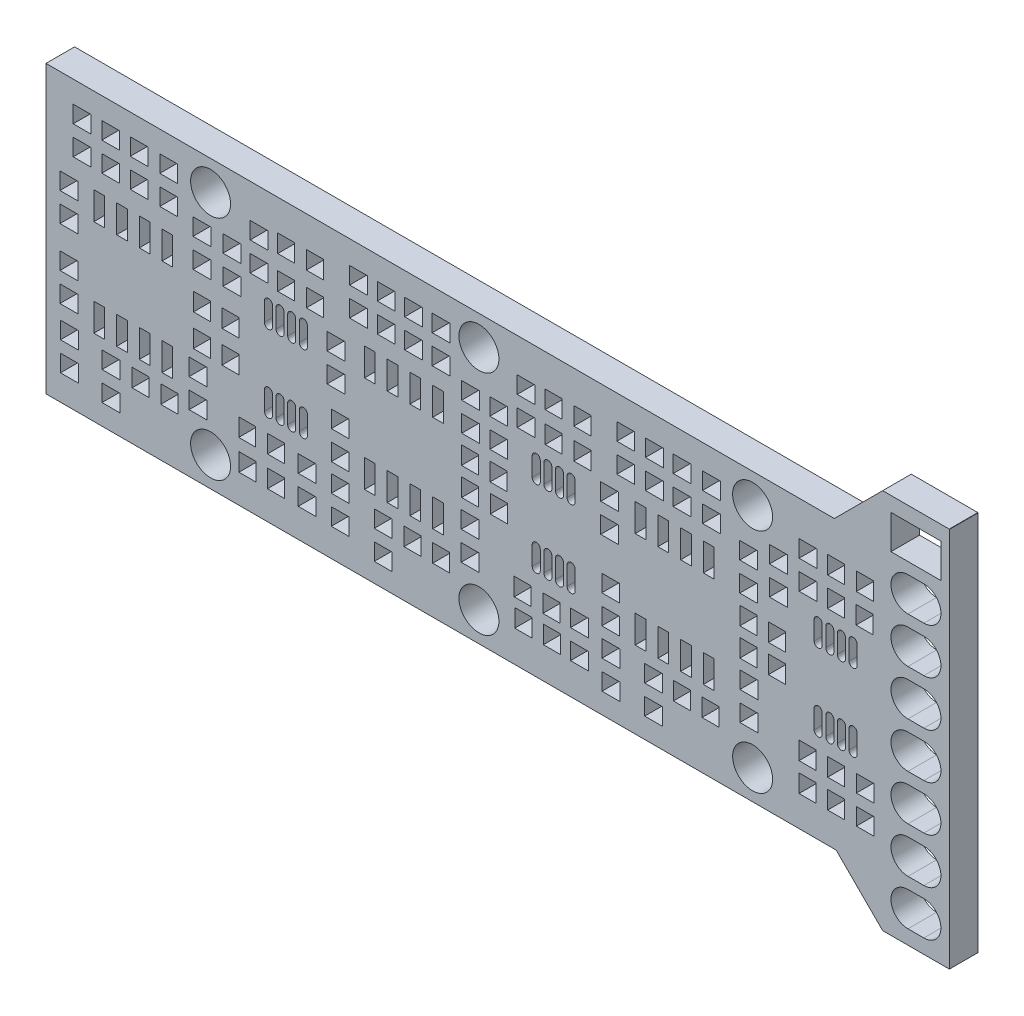
SolidWorks part; units mm, degrees
ref_plane "Plan de face" through (0, 0, 0) normal (0, 0, 1) x (1, 0, 0)
ref_plane "Plan de dessus" through (0, 0, 0) normal (0, 1, 0) x (1, 0, 0)
ref_plane "Plan de droite" through (0, 0, 0) normal (1, 0, 0) x (0, 0, -1)
sketch "Model" plane through (0, 0, 0) normal (0, 0, 1) x (1, 0, 0)
  line L0 (-3.267, 1.8825) -> (-0.473, 1.8825)
  line L1 (-0.473, 1.8825) -> (-0.473, -0.0225)
  line L2 (-0.473, -0.0225) -> (-3.267, -0.0225)
  line L3 (-3.267, -0.0225) -> (-3.267, 1.8825)
  line L4 (-1.4255, -2.5625) -> (-2.3145, -2.5625)
  line L5 (-2.3145, -0.6575) -> (-1.4255, -0.6575)
  line L6 (-1.4255, -5.1025) -> (-2.3145, -5.1025)
  line L7 (-2.3145, -3.1975) -> (-1.4255, -3.1975)
  line L8 (-1.4255, -7.6425) -> (-2.3145, -7.6425)
  line L9 (-2.3145, -5.7375) -> (-1.4255, -5.7375)
  line L10 (-1.4255, -10.1825) -> (-2.3145, -10.1825)
  line L11 (-2.3145, -8.2775) -> (-1.4255, -8.2775)
  line L12 (-1.4255, -12.7225) -> (-2.3145, -12.7225)
  line L13 (-2.3145, -10.8175) -> (-1.4255, -10.8175)
  line L14 (-1.4255, -15.2625) -> (-2.3145, -15.2625)
  line L15 (-2.3145, -13.3575) -> (-1.4255, -13.3575)
  line L16 (-1.4255, -17.8025) -> (-2.3145, -17.8025)
  line L17 (-2.3145, -15.8975) -> (-1.4255, -15.8975)
  line L18 (-37.84, -9.685) -> (-37.84, -10.735)
  line L19 (-38.29, -10.735) -> (-38.29, -9.685)
  line L20 (-37.19, -9.685) -> (-37.19, -10.735)
  line L21 (-37.64, -10.735) -> (-37.64, -9.685)
  line L22 (-36.54, -9.685) -> (-36.54, -10.735)
  line L23 (-36.99, -10.735) -> (-36.99, -9.685)
  line L24 (-35.89, -9.685) -> (-35.89, -10.735)
  line L25 (-36.34, -10.735) -> (-36.34, -9.685)
  line L26 (-35.89, -5.385) -> (-35.89, -6.435)
  line L27 (-36.34, -6.435) -> (-36.34, -5.385)
  line L28 (-36.54, -5.385) -> (-36.54, -6.435)
  line L29 (-36.99, -6.435) -> (-36.99, -5.385)
  line L30 (-37.19, -5.385) -> (-37.19, -6.435)
  line L31 (-37.64, -6.435) -> (-37.64, -5.385)
  line L32 (-37.84, -5.385) -> (-37.84, -6.435)
  line L33 (-38.29, -6.435) -> (-38.29, -5.385)
  line L34 (-22.87, -9.705) -> (-22.87, -10.755)
  line L35 (-23.32, -10.755) -> (-23.32, -9.705)
  line L36 (-22.22, -9.705) -> (-22.22, -10.755)
  line L37 (-22.67, -10.755) -> (-22.67, -9.705)
  line L38 (-21.57, -9.705) -> (-21.57, -10.755)
  line L39 (-22.02, -10.755) -> (-22.02, -9.705)
  line L40 (-20.92, -9.705) -> (-20.92, -10.755)
  line L41 (-21.37, -10.755) -> (-21.37, -9.705)
  line L42 (-20.92, -5.405) -> (-20.92, -6.455)
  line L43 (-21.37, -6.455) -> (-21.37, -5.405)
  line L44 (-21.57, -5.405) -> (-21.57, -6.455)
  line L45 (-22.02, -6.455) -> (-22.02, -5.405)
  line L46 (-22.22, -5.405) -> (-22.22, -6.455)
  line L47 (-22.67, -6.455) -> (-22.67, -5.405)
  line L48 (-22.87, -5.405) -> (-22.87, -6.455)
  line L49 (-23.32, -6.455) -> (-23.32, -5.405)
  line L50 (-7.11, -9.745) -> (-7.11, -10.795)
  line L51 (-7.56, -10.795) -> (-7.56, -9.745)
  line L52 (-6.46, -9.745) -> (-6.46, -10.795)
  line L53 (-6.91, -10.795) -> (-6.91, -9.745)
  line L54 (-5.81, -9.745) -> (-5.81, -10.795)
  line L55 (-6.26, -10.795) -> (-6.26, -9.745)
  line L56 (-5.16, -9.745) -> (-5.16, -10.795)
  line L57 (-5.61, -10.795) -> (-5.61, -9.745)
  line L58 (-5.16, -5.445) -> (-5.16, -6.495)
  line L59 (-5.61, -6.495) -> (-5.61, -5.445)
  line L60 (-5.81, -5.445) -> (-5.81, -6.495)
  line L61 (-6.26, -6.495) -> (-6.26, -5.445)
  line L62 (-6.46, -5.445) -> (-6.46, -6.495)
  line L63 (-6.91, -6.495) -> (-6.91, -5.445)
  line L64 (-7.11, -5.445) -> (-7.11, -6.495)
  line L65 (-7.56, -6.495) -> (-7.56, -5.445)
  line L66 (-44.015, -4.775) -> (-43.415, -4.775)
  line L67 (-43.415, -4.775) -> (-43.415, -6.325)
  line L68 (-43.415, -6.325) -> (-44.015, -6.325)
  line L69 (-44.015, -6.325) -> (-44.015, -4.775)
  line L70 (-45.285, -4.775) -> (-44.685, -4.775)
  line L71 (-44.685, -4.775) -> (-44.685, -6.325)
  line L72 (-44.685, -6.325) -> (-45.285, -6.325)
  line L73 (-45.285, -6.325) -> (-45.285, -4.775)
  line L74 (-46.555, -4.775) -> (-45.955, -4.775)
  line L75 (-45.955, -4.775) -> (-45.955, -6.325)
  line L76 (-45.955, -6.325) -> (-46.555, -6.325)
  line L77 (-46.555, -6.325) -> (-46.555, -4.775)
  line L78 (-47.825, -4.775) -> (-47.225, -4.775)
  line L79 (-47.225, -4.775) -> (-47.225, -6.325)
  line L80 (-47.225, -6.325) -> (-47.825, -6.325)
  line L81 (-47.825, -6.325) -> (-47.825, -4.775)
  line L82 (-47.825, -10.175) -> (-47.225, -10.175)
  line L83 (-47.225, -10.175) -> (-47.225, -11.725)
  line L84 (-47.225, -11.725) -> (-47.825, -11.725)
  line L85 (-47.825, -11.725) -> (-47.825, -10.175)
  line L86 (-46.555, -10.175) -> (-45.955, -10.175)
  line L87 (-45.955, -10.175) -> (-45.955, -11.725)
  line L88 (-45.955, -11.725) -> (-46.555, -11.725)
  line L89 (-46.555, -11.725) -> (-46.555, -10.175)
  line L90 (-45.285, -10.175) -> (-44.685, -10.175)
  line L91 (-44.685, -10.175) -> (-44.685, -11.725)
  line L92 (-44.685, -11.725) -> (-45.285, -11.725)
  line L93 (-45.285, -11.725) -> (-45.285, -10.175)
  line L94 (-44.015, -10.175) -> (-43.415, -10.175)
  line L95 (-43.415, -10.175) -> (-43.415, -11.725)
  line L96 (-43.415, -11.725) -> (-44.015, -11.725)
  line L97 (-44.015, -11.725) -> (-44.015, -10.175)
  line L98 (-28.885, -4.775) -> (-28.285, -4.775)
  line L99 (-28.285, -4.775) -> (-28.285, -6.325)
  line L100 (-28.285, -6.325) -> (-28.885, -6.325)
  line L101 (-28.885, -6.325) -> (-28.885, -4.775)
  line L102 (-30.155, -4.775) -> (-29.555, -4.775)
  line L103 (-29.555, -4.775) -> (-29.555, -6.325)
  line L104 (-29.555, -6.325) -> (-30.155, -6.325)
  line L105 (-30.155, -6.325) -> (-30.155, -4.775)
  line L106 (-31.425, -4.775) -> (-30.825, -4.775)
  line L107 (-30.825, -4.775) -> (-30.825, -6.325)
  line L108 (-30.825, -6.325) -> (-31.425, -6.325)
  line L109 (-31.425, -6.325) -> (-31.425, -4.775)
  line L110 (-32.695, -4.775) -> (-32.095, -4.775)
  line L111 (-32.095, -4.775) -> (-32.095, -6.325)
  line L112 (-32.095, -6.325) -> (-32.695, -6.325)
  line L113 (-32.695, -6.325) -> (-32.695, -4.775)
  line L114 (-32.695, -10.175) -> (-32.095, -10.175)
  line L115 (-32.095, -10.175) -> (-32.095, -11.725)
  line L116 (-32.095, -11.725) -> (-32.695, -11.725)
  line L117 (-32.695, -11.725) -> (-32.695, -10.175)
  line L118 (-31.425, -10.175) -> (-30.825, -10.175)
  line L119 (-30.825, -10.175) -> (-30.825, -11.725)
  line L120 (-30.825, -11.725) -> (-31.425, -11.725)
  line L121 (-31.425, -11.725) -> (-31.425, -10.175)
  line L122 (-30.155, -10.175) -> (-29.555, -10.175)
  line L123 (-29.555, -10.175) -> (-29.555, -11.725)
  line L124 (-29.555, -11.725) -> (-30.155, -11.725)
  line L125 (-30.155, -11.725) -> (-30.155, -10.175)
  line L126 (-28.885, -10.175) -> (-28.285, -10.175)
  line L127 (-28.285, -10.175) -> (-28.285, -11.725)
  line L128 (-28.285, -11.725) -> (-28.885, -11.725)
  line L129 (-28.885, -11.725) -> (-28.885, -10.175)
  line L130 (-13.755, -4.745) -> (-13.155, -4.745)
  line L131 (-13.155, -4.745) -> (-13.155, -6.295)
  line L132 (-13.155, -6.295) -> (-13.755, -6.295)
  line L133 (-13.755, -6.295) -> (-13.755, -4.745)
  line L134 (-15.025, -4.745) -> (-14.425, -4.745)
  line L135 (-14.425, -4.745) -> (-14.425, -6.295)
  line L136 (-14.425, -6.295) -> (-15.025, -6.295)
  line L137 (-15.025, -6.295) -> (-15.025, -4.745)
  line L138 (-16.295, -4.745) -> (-15.695, -4.745)
  line L139 (-15.695, -4.745) -> (-15.695, -6.295)
  line L140 (-15.695, -6.295) -> (-16.295, -6.295)
  line L141 (-16.295, -6.295) -> (-16.295, -4.745)
  line L142 (-17.565, -4.745) -> (-16.965, -4.745)
  line L143 (-16.965, -4.745) -> (-16.965, -6.295)
  line L144 (-16.965, -6.295) -> (-17.565, -6.295)
  line L145 (-17.565, -6.295) -> (-17.565, -4.745)
  line L146 (-17.565, -10.145) -> (-16.965, -10.145)
  line L147 (-16.965, -10.145) -> (-16.965, -11.695)
  line L148 (-16.965, -11.695) -> (-17.565, -11.695)
  line L149 (-17.565, -11.695) -> (-17.565, -10.145)
  line L150 (-16.295, -10.145) -> (-15.695, -10.145)
  line L151 (-15.695, -10.145) -> (-15.695, -11.695)
  line L152 (-15.695, -11.695) -> (-16.295, -11.695)
  line L153 (-16.295, -11.695) -> (-16.295, -10.145)
  line L154 (-15.025, -10.145) -> (-14.425, -10.145)
  line L155 (-14.425, -10.145) -> (-14.425, -11.695)
  line L156 (-14.425, -11.695) -> (-15.025, -11.695)
  line L157 (-15.025, -11.695) -> (-15.025, -10.145)
  line L158 (-13.755, -10.145) -> (-13.155, -10.145)
  line L159 (-13.155, -10.145) -> (-13.155, -11.695)
  line L160 (-13.155, -11.695) -> (-13.755, -11.695)
  line L161 (-13.755, -11.695) -> (-13.755, -10.145)
  line L162 (-38.775, -12.72) -> (-39.725, -12.72)
  line L163 (-39.725, -12.72) -> (-39.725, -11.72)
  line L164 (-39.725, -11.72) -> (-38.775, -11.72)
  line L165 (-38.775, -11.72) -> (-38.775, -12.72)
  line L166 (-37.175, -12.72) -> (-38.125, -12.72)
  line L167 (-38.125, -12.72) -> (-38.125, -11.72)
  line L168 (-38.125, -11.72) -> (-37.175, -11.72)
  line L169 (-37.175, -11.72) -> (-37.175, -12.72)
  line L170 (-48.98, -2.165) -> (-48.98, -1.215)
  line L171 (-48.98, -1.215) -> (-47.98, -1.215)
  line L172 (-47.98, -1.215) -> (-47.98, -2.165)
  line L173 (-47.98, -2.165) -> (-48.98, -2.165)
  line L174 (-48.98, -3.765) -> (-48.98, -2.815)
  line L175 (-48.98, -2.815) -> (-47.98, -2.815)
  line L176 (-47.98, -2.815) -> (-47.98, -3.765)
  line L177 (-47.98, -3.765) -> (-48.98, -3.765)
  line L178 (-49.72, -9.635) -> (-49.72, -8.685)
  line L179 (-49.72, -8.685) -> (-48.72, -8.685)
  line L180 (-48.72, -8.685) -> (-48.72, -9.635)
  line L181 (-48.72, -9.635) -> (-49.72, -9.635)
  line L182 (-49.72, -11.235) -> (-49.72, -10.285)
  line L183 (-49.72, -10.285) -> (-48.72, -10.285)
  line L184 (-48.72, -10.285) -> (-48.72, -11.235)
  line L185 (-48.72, -11.235) -> (-49.72, -11.235)
  line L186 (-49.69, -12.975) -> (-49.69, -12.025)
  line L187 (-49.69, -12.025) -> (-48.69, -12.025)
  line L188 (-48.69, -12.025) -> (-48.69, -12.975)
  line L189 (-48.69, -12.975) -> (-49.69, -12.975)
  line L190 (-49.69, -14.575) -> (-49.69, -13.625)
  line L191 (-49.69, -13.625) -> (-48.69, -13.625)
  line L192 (-48.69, -13.625) -> (-48.69, -14.575)
  line L193 (-48.69, -14.575) -> (-49.69, -14.575)
  line L194 (-41.315, -9.69) -> (-42.265, -9.69)
  line L195 (-42.265, -9.69) -> (-42.265, -8.69)
  line L196 (-42.265, -8.69) -> (-41.315, -8.69)
  line L197 (-41.315, -8.69) -> (-41.315, -9.69)
  line L198 (-39.715, -9.69) -> (-40.665, -9.69)
  line L199 (-40.665, -9.69) -> (-40.665, -8.69)
  line L200 (-40.665, -8.69) -> (-39.715, -8.69)
  line L201 (-39.715, -8.69) -> (-39.715, -9.69)
  line L202 (-46.37, -13.905) -> (-46.37, -14.855)
  line L203 (-46.37, -14.855) -> (-47.37, -14.855)
  line L204 (-47.37, -14.855) -> (-47.37, -13.905)
  line L205 (-47.37, -13.905) -> (-46.37, -13.905)
  line L206 (-46.37, -12.305) -> (-46.37, -13.255)
  line L207 (-46.37, -13.255) -> (-47.37, -13.255)
  line L208 (-47.37, -13.255) -> (-47.37, -12.305)
  line L209 (-47.37, -12.305) -> (-46.37, -12.305)
  line L210 (-41.305, -7.91) -> (-42.255, -7.91)
  line L211 (-42.255, -7.91) -> (-42.255, -6.91)
  line L212 (-42.255, -6.91) -> (-41.305, -6.91)
  line L213 (-41.305, -6.91) -> (-41.305, -7.91)
  line L214 (-39.705, -7.91) -> (-40.655, -7.91)
  line L215 (-40.655, -7.91) -> (-40.655, -6.91)
  line L216 (-40.655, -6.91) -> (-39.705, -6.91)
  line L217 (-39.705, -6.91) -> (-39.705, -7.91)
  line L218 (-49.72, -5.765) -> (-49.72, -4.815)
  line L219 (-49.72, -4.815) -> (-48.72, -4.815)
  line L220 (-48.72, -4.815) -> (-48.72, -5.765)
  line L221 (-48.72, -5.765) -> (-49.72, -5.765)
  line L222 (-49.72, -7.365) -> (-49.72, -6.415)
  line L223 (-49.72, -6.415) -> (-48.72, -6.415)
  line L224 (-48.72, -6.415) -> (-48.72, -7.365)
  line L225 (-48.72, -7.365) -> (-49.72, -7.365)
  line L226 (-44.085, -12.3) -> (-43.135, -12.3)
  line L227 (-43.135, -12.3) -> (-43.135, -13.3)
  line L228 (-43.135, -13.3) -> (-44.085, -13.3)
  line L229 (-44.085, -13.3) -> (-44.085, -12.3)
  line L230 (-45.685, -12.3) -> (-44.735, -12.3)
  line L231 (-44.735, -12.3) -> (-44.735, -13.3)
  line L232 (-44.735, -13.3) -> (-45.685, -13.3)
  line L233 (-45.685, -13.3) -> (-45.685, -12.3)
  line L234 (-36.595, -4.56) -> (-37.545, -4.56)
  line L235 (-37.545, -4.56) -> (-37.545, -3.56)
  line L236 (-37.545, -3.56) -> (-36.595, -3.56)
  line L237 (-36.595, -3.56) -> (-36.595, -4.56)
  line L238 (-34.995, -4.56) -> (-35.945, -4.56)
  line L239 (-35.945, -4.56) -> (-35.945, -3.56)
  line L240 (-35.945, -3.56) -> (-34.995, -3.56)
  line L241 (-34.995, -3.56) -> (-34.995, -4.56)
  line L242 (-45.79, -2.145) -> (-45.79, -1.195)
  line L243 (-45.79, -1.195) -> (-44.79, -1.195)
  line L244 (-44.79, -1.195) -> (-44.79, -2.145)
  line L245 (-44.79, -2.145) -> (-45.79, -2.145)
  line L246 (-45.79, -3.745) -> (-45.79, -2.795)
  line L247 (-45.79, -2.795) -> (-44.79, -2.795)
  line L248 (-44.79, -2.795) -> (-44.79, -3.745)
  line L249 (-44.79, -3.745) -> (-45.79, -3.745)
  line L250 (-39.61, -4.895) -> (-39.61, -5.845)
  line L251 (-39.61, -5.845) -> (-40.61, -5.845)
  line L252 (-40.61, -5.845) -> (-40.61, -4.895)
  line L253 (-40.61, -4.895) -> (-39.61, -4.895)
  line L254 (-39.61, -3.295) -> (-39.61, -4.245)
  line L255 (-39.61, -4.245) -> (-40.61, -4.245)
  line L256 (-40.61, -4.245) -> (-40.61, -3.295)
  line L257 (-40.61, -3.295) -> (-39.61, -3.295)
  line L258 (-43.14, -2.795) -> (-43.14, -3.745)
  line L259 (-43.14, -3.745) -> (-44.14, -3.745)
  line L260 (-44.14, -3.745) -> (-44.14, -2.795)
  line L261 (-44.14, -2.795) -> (-43.14, -2.795)
  line L262 (-43.14, -1.195) -> (-43.14, -2.145)
  line L263 (-43.14, -2.145) -> (-44.14, -2.145)
  line L264 (-44.14, -2.145) -> (-44.14, -1.195)
  line L265 (-44.14, -1.195) -> (-43.14, -1.195)
  line L266 (-38.115, -13.4) -> (-37.165, -13.4)
  line L267 (-37.165, -13.4) -> (-37.165, -14.4)
  line L268 (-37.165, -14.4) -> (-38.115, -14.4)
  line L269 (-38.115, -14.4) -> (-38.115, -13.4)
  line L270 (-39.715, -13.4) -> (-38.765, -13.4)
  line L271 (-38.765, -13.4) -> (-38.765, -14.4)
  line L272 (-38.765, -14.4) -> (-39.715, -14.4)
  line L273 (-39.715, -14.4) -> (-39.715, -13.4)
  line L274 (-42.5, -11.165) -> (-42.5, -10.215)
  line L275 (-42.5, -10.215) -> (-41.5, -10.215)
  line L276 (-41.5, -10.215) -> (-41.5, -11.165)
  line L277 (-41.5, -11.165) -> (-42.5, -11.165)
  line L278 (-42.5, -12.765) -> (-42.5, -11.815)
  line L279 (-42.5, -11.815) -> (-41.5, -11.815)
  line L280 (-41.5, -11.815) -> (-41.5, -12.765)
  line L281 (-41.5, -12.765) -> (-42.5, -12.765)
  line L282 (-41.28, -4.915) -> (-41.28, -5.865)
  line L283 (-41.28, -5.865) -> (-42.28, -5.865)
  line L284 (-42.28, -5.865) -> (-42.28, -4.915)
  line L285 (-42.28, -4.915) -> (-41.28, -4.915)
  line L286 (-41.28, -3.315) -> (-41.28, -4.265)
  line L287 (-41.28, -4.265) -> (-42.28, -4.265)
  line L288 (-42.28, -4.265) -> (-42.28, -3.315)
  line L289 (-42.28, -3.315) -> (-41.28, -3.315)
  line L290 (-39.09, -2.845) -> (-39.09, -1.895)
  line L291 (-39.09, -1.895) -> (-38.09, -1.895)
  line L292 (-38.09, -1.895) -> (-38.09, -2.845)
  line L293 (-38.09, -2.845) -> (-39.09, -2.845)
  line L294 (-39.09, -4.445) -> (-39.09, -3.495)
  line L295 (-39.09, -3.495) -> (-38.09, -3.495)
  line L296 (-38.09, -3.495) -> (-38.09, -4.445)
  line L297 (-38.09, -4.445) -> (-39.09, -4.445)
  line L298 (-36.595, -2.73) -> (-37.545, -2.73)
  line L299 (-37.545, -2.73) -> (-37.545, -1.73)
  line L300 (-37.545, -1.73) -> (-36.595, -1.73)
  line L301 (-36.595, -1.73) -> (-36.595, -2.73)
  line L302 (-34.995, -2.73) -> (-35.945, -2.73)
  line L303 (-35.945, -2.73) -> (-35.945, -1.73)
  line L304 (-35.945, -1.73) -> (-34.995, -1.73)
  line L305 (-34.995, -1.73) -> (-34.995, -2.73)
  line L306 (-36.4, -12.795) -> (-36.4, -11.845)
  line L307 (-36.4, -11.845) -> (-35.4, -11.845)
  line L308 (-35.4, -11.845) -> (-35.4, -12.795)
  line L309 (-35.4, -12.795) -> (-36.4, -12.795)
  line L310 (-36.4, -14.395) -> (-36.4, -13.445)
  line L311 (-36.4, -13.445) -> (-35.4, -13.445)
  line L312 (-35.4, -13.445) -> (-35.4, -14.395)
  line L313 (-35.4, -14.395) -> (-36.4, -14.395)
  line L314 (-46.38, -2.805) -> (-46.38, -3.755)
  line L315 (-46.38, -3.755) -> (-47.38, -3.755)
  line L316 (-47.38, -3.755) -> (-47.38, -2.805)
  line L317 (-47.38, -2.805) -> (-46.38, -2.805)
  line L318 (-46.38, -1.205) -> (-46.38, -2.155)
  line L319 (-46.38, -2.155) -> (-47.38, -2.155)
  line L320 (-47.38, -2.155) -> (-47.38, -1.205)
  line L321 (-47.38, -1.205) -> (-46.38, -1.205)
  line L322 (-23.375, -12.74) -> (-24.325, -12.74)
  line L323 (-24.325, -12.74) -> (-24.325, -11.74)
  line L324 (-24.325, -11.74) -> (-23.375, -11.74)
  line L325 (-23.375, -11.74) -> (-23.375, -12.74)
  line L326 (-21.775, -12.74) -> (-22.725, -12.74)
  line L327 (-22.725, -12.74) -> (-22.725, -11.74)
  line L328 (-22.725, -11.74) -> (-21.775, -11.74)
  line L329 (-21.775, -11.74) -> (-21.775, -12.74)
  line L330 (-33.53, -2.245) -> (-33.53, -1.295)
  line L331 (-33.53, -1.295) -> (-32.53, -1.295)
  line L332 (-32.53, -1.295) -> (-32.53, -2.245)
  line L333 (-32.53, -2.245) -> (-33.53, -2.245)
  line L334 (-33.53, -3.845) -> (-33.53, -2.895)
  line L335 (-33.53, -2.895) -> (-32.53, -2.895)
  line L336 (-32.53, -2.895) -> (-32.53, -3.845)
  line L337 (-32.53, -3.845) -> (-33.53, -3.845)
  line L338 (-34.55, -9.705) -> (-34.55, -8.755)
  line L339 (-34.55, -8.755) -> (-33.55, -8.755)
  line L340 (-33.55, -8.755) -> (-33.55, -9.705)
  line L341 (-33.55, -9.705) -> (-34.55, -9.705)
  line L342 (-34.55, -11.305) -> (-34.55, -10.355)
  line L343 (-34.55, -10.355) -> (-33.55, -10.355)
  line L344 (-33.55, -10.355) -> (-33.55, -11.305)
  line L345 (-33.55, -11.305) -> (-34.55, -11.305)
  line L346 (-34.55, -12.835) -> (-34.55, -11.885)
  line L347 (-34.55, -11.885) -> (-33.55, -11.885)
  line L348 (-33.55, -11.885) -> (-33.55, -12.835)
  line L349 (-33.55, -12.835) -> (-34.55, -12.835)
  line L350 (-34.55, -14.435) -> (-34.55, -13.485)
  line L351 (-34.55, -13.485) -> (-33.55, -13.485)
  line L352 (-33.55, -13.485) -> (-33.55, -14.435)
  line L353 (-33.55, -14.435) -> (-34.55, -14.435)
  line L354 (-26.315, -9.4) -> (-27.265, -9.4)
  line L355 (-27.265, -9.4) -> (-27.265, -8.4)
  line L356 (-27.265, -8.4) -> (-26.315, -8.4)
  line L357 (-26.315, -8.4) -> (-26.315, -9.4)
  line L358 (-24.715, -9.4) -> (-25.665, -9.4)
  line L359 (-25.665, -9.4) -> (-25.665, -8.4)
  line L360 (-25.665, -8.4) -> (-24.715, -8.4)
  line L361 (-24.715, -8.4) -> (-24.715, -9.4)
  line L362 (-32.15, -13.335) -> (-32.15, -12.385)
  line L363 (-32.15, -12.385) -> (-31.15, -12.385)
  line L364 (-31.15, -12.385) -> (-31.15, -13.335)
  line L365 (-31.15, -13.335) -> (-32.15, -13.335)
  line L366 (-32.15, -14.935) -> (-32.15, -13.985)
  line L367 (-32.15, -13.985) -> (-31.15, -13.985)
  line L368 (-31.15, -13.985) -> (-31.15, -14.935)
  line L369 (-31.15, -14.935) -> (-32.15, -14.935)
  line L370 (-26.325, -7.85) -> (-27.275, -7.85)
  line L371 (-27.275, -7.85) -> (-27.275, -6.85)
  line L372 (-27.275, -6.85) -> (-26.325, -6.85)
  line L373 (-26.325, -6.85) -> (-26.325, -7.85)
  line L374 (-24.725, -7.85) -> (-25.675, -7.85)
  line L375 (-25.675, -7.85) -> (-25.675, -6.85)
  line L376 (-25.675, -6.85) -> (-24.725, -6.85)
  line L377 (-24.725, -6.85) -> (-24.725, -7.85)
  line L378 (-34.79, -6.065) -> (-34.79, -5.115)
  line L379 (-34.79, -5.115) -> (-33.79, -5.115)
  line L380 (-33.79, -5.115) -> (-33.79, -6.065)
  line L381 (-33.79, -6.065) -> (-34.79, -6.065)
  line L382 (-34.79, -7.665) -> (-34.79, -6.715)
  line L383 (-34.79, -6.715) -> (-33.79, -6.715)
  line L384 (-33.79, -6.715) -> (-33.79, -7.665)
  line L385 (-33.79, -7.665) -> (-34.79, -7.665)
  line L386 (-28.885, -12.39) -> (-27.935, -12.39)
  line L387 (-27.935, -12.39) -> (-27.935, -13.39)
  line L388 (-27.935, -13.39) -> (-28.885, -13.39)
  line L389 (-28.885, -13.39) -> (-28.885, -12.39)
  line L390 (-30.485, -12.39) -> (-29.535, -12.39)
  line L391 (-29.535, -12.39) -> (-29.535, -13.39)
  line L392 (-29.535, -13.39) -> (-30.485, -13.39)
  line L393 (-30.485, -13.39) -> (-30.485, -12.39)
  line L394 (-21.645, -4.5) -> (-22.595, -4.5)
  line L395 (-22.595, -4.5) -> (-22.595, -3.5)
  line L396 (-22.595, -3.5) -> (-21.645, -3.5)
  line L397 (-21.645, -3.5) -> (-21.645, -4.5)
  line L398 (-20.045, -4.5) -> (-20.995, -4.5)
  line L399 (-20.995, -4.5) -> (-20.995, -3.5)
  line L400 (-20.995, -3.5) -> (-20.045, -3.5)
  line L401 (-20.045, -3.5) -> (-20.045, -4.5)
  line L402 (-30.45, -2.245) -> (-30.45, -1.295)
  line L403 (-30.45, -1.295) -> (-29.45, -1.295)
  line L404 (-29.45, -1.295) -> (-29.45, -2.245)
  line L405 (-29.45, -2.245) -> (-30.45, -2.245)
  line L406 (-30.45, -3.845) -> (-30.45, -2.895)
  line L407 (-30.45, -2.895) -> (-29.45, -2.895)
  line L408 (-29.45, -2.895) -> (-29.45, -3.845)
  line L409 (-29.45, -3.845) -> (-30.45, -3.845)
  line L410 (-24.69, -5.325) -> (-24.69, -6.275)
  line L411 (-24.69, -6.275) -> (-25.69, -6.275)
  line L412 (-25.69, -6.275) -> (-25.69, -5.325)
  line L413 (-25.69, -5.325) -> (-24.69, -5.325)
  line L414 (-24.69, -3.725) -> (-24.69, -4.675)
  line L415 (-24.69, -4.675) -> (-25.69, -4.675)
  line L416 (-25.69, -4.675) -> (-25.69, -3.725)
  line L417 (-25.69, -3.725) -> (-24.69, -3.725)
  line L418 (-27.91, -2.895) -> (-27.91, -3.845)
  line L419 (-27.91, -3.845) -> (-28.91, -3.845)
  line L420 (-28.91, -3.845) -> (-28.91, -2.895)
  line L421 (-28.91, -2.895) -> (-27.91, -2.895)
  line L422 (-27.91, -1.295) -> (-27.91, -2.245)
  line L423 (-27.91, -2.245) -> (-28.91, -2.245)
  line L424 (-28.91, -2.245) -> (-28.91, -1.295)
  line L425 (-28.91, -1.295) -> (-27.91, -1.295)
  line L426 (-7.455, -12.71) -> (-8.405, -12.71)
  line L427 (-8.405, -12.71) -> (-8.405, -11.71)
  line L428 (-8.405, -11.71) -> (-7.455, -11.71)
  line L429 (-7.455, -11.71) -> (-7.455, -12.71)
  line L430 (-5.855, -12.71) -> (-6.805, -12.71)
  line L431 (-6.805, -12.71) -> (-6.805, -11.71)
  line L432 (-6.805, -11.71) -> (-5.855, -11.71)
  line L433 (-5.855, -11.71) -> (-5.855, -12.71)
  line L434 (-18.59, -2.335) -> (-18.59, -1.385)
  line L435 (-18.59, -1.385) -> (-17.59, -1.385)
  line L436 (-17.59, -1.385) -> (-17.59, -2.335)
  line L437 (-17.59, -2.335) -> (-18.59, -2.335)
  line L438 (-18.59, -3.935) -> (-18.59, -2.985)
  line L439 (-18.59, -2.985) -> (-17.59, -2.985)
  line L440 (-17.59, -2.985) -> (-17.59, -3.935)
  line L441 (-17.59, -3.935) -> (-18.59, -3.935)
  line L442 (-19.43, -10.095) -> (-19.43, -9.145)
  line L443 (-19.43, -9.145) -> (-18.43, -9.145)
  line L444 (-18.43, -9.145) -> (-18.43, -10.095)
  line L445 (-18.43, -10.095) -> (-19.43, -10.095)
  line L446 (-19.43, -11.695) -> (-19.43, -10.745)
  line L447 (-19.43, -10.745) -> (-18.43, -10.745)
  line L448 (-18.43, -10.745) -> (-18.43, -11.695)
  line L449 (-18.43, -11.695) -> (-19.43, -11.695)
  line L450 (-19.42, -13.255) -> (-19.42, -12.305)
  line L451 (-19.42, -12.305) -> (-18.42, -12.305)
  line L452 (-18.42, -12.305) -> (-18.42, -13.255)
  line L453 (-18.42, -13.255) -> (-19.42, -13.255)
  line L454 (-19.42, -14.855) -> (-19.42, -13.905)
  line L455 (-19.42, -13.905) -> (-18.42, -13.905)
  line L456 (-18.42, -13.905) -> (-18.42, -14.855)
  line L457 (-18.42, -14.855) -> (-19.42, -14.855)
  line L458 (-10.765, -9.4) -> (-11.715, -9.4)
  line L459 (-11.715, -9.4) -> (-11.715, -8.4)
  line L460 (-11.715, -8.4) -> (-10.765, -8.4)
  line L461 (-10.765, -8.4) -> (-10.765, -9.4)
  line L462 (-9.165, -9.4) -> (-10.115, -9.4)
  line L463 (-10.115, -9.4) -> (-10.115, -8.4)
  line L464 (-10.115, -8.4) -> (-9.165, -8.4)
  line L465 (-9.165, -8.4) -> (-9.165, -9.4)
  line L466 (-17.03, -13.265) -> (-17.03, -12.315)
  line L467 (-17.03, -12.315) -> (-16.03, -12.315)
  line L468 (-16.03, -12.315) -> (-16.03, -13.265)
  line L469 (-16.03, -13.265) -> (-17.03, -13.265)
  line L470 (-17.03, -14.865) -> (-17.03, -13.915)
  line L471 (-17.03, -13.915) -> (-16.03, -13.915)
  line L472 (-16.03, -13.915) -> (-16.03, -14.865)
  line L473 (-16.03, -14.865) -> (-17.03, -14.865)
  line L474 (-10.765, -7.84) -> (-11.715, -7.84)
  line L475 (-11.715, -7.84) -> (-11.715, -6.84)
  line L476 (-11.715, -6.84) -> (-10.765, -6.84)
  line L477 (-10.765, -6.84) -> (-10.765, -7.84)
  line L478 (-9.165, -7.84) -> (-10.115, -7.84)
  line L479 (-10.115, -7.84) -> (-10.115, -6.84)
  line L480 (-10.115, -6.84) -> (-9.165, -6.84)
  line L481 (-9.165, -6.84) -> (-9.165, -7.84)
  line L482 (-19.49, -5.695) -> (-19.49, -4.745)
  line L483 (-19.49, -4.745) -> (-18.49, -4.745)
  line L484 (-18.49, -4.745) -> (-18.49, -5.695)
  line L485 (-18.49, -5.695) -> (-19.49, -5.695)
  line L486 (-19.49, -7.295) -> (-19.49, -6.345)
  line L487 (-19.49, -6.345) -> (-18.49, -6.345)
  line L488 (-18.49, -6.345) -> (-18.49, -7.295)
  line L489 (-18.49, -7.295) -> (-19.49, -7.295)
  line L490 (-13.825, -12.33) -> (-12.875, -12.33)
  line L491 (-12.875, -12.33) -> (-12.875, -13.33)
  line L492 (-12.875, -13.33) -> (-13.825, -13.33)
  line L493 (-13.825, -13.33) -> (-13.825, -12.33)
  line L494 (-15.425, -12.33) -> (-14.475, -12.33)
  line L495 (-14.475, -12.33) -> (-14.475, -13.33)
  line L496 (-14.475, -13.33) -> (-15.425, -13.33)
  line L497 (-15.425, -13.33) -> (-15.425, -12.33)
  line L498 (-5.865, -4.55) -> (-6.815, -4.55)
  line L499 (-6.815, -4.55) -> (-6.815, -3.55)
  line L500 (-6.815, -3.55) -> (-5.865, -3.55)
  line L501 (-5.865, -3.55) -> (-5.865, -4.55)
  line L502 (-4.265, -4.55) -> (-5.215, -4.55)
  line L503 (-5.215, -4.55) -> (-5.215, -3.55)
  line L504 (-5.215, -3.55) -> (-4.265, -3.55)
  line L505 (-4.265, -3.55) -> (-4.265, -4.55)
  line L506 (-15.44, -2.325) -> (-15.44, -1.375)
  line L507 (-15.44, -1.375) -> (-14.44, -1.375)
  line L508 (-14.44, -1.375) -> (-14.44, -2.325)
  line L509 (-14.44, -2.325) -> (-15.44, -2.325)
  line L510 (-15.44, -3.925) -> (-15.44, -2.975)
  line L511 (-15.44, -2.975) -> (-14.44, -2.975)
  line L512 (-14.44, -2.975) -> (-14.44, -3.925)
  line L513 (-14.44, -3.925) -> (-15.44, -3.925)
  line L514 (-9.06, -4.665) -> (-9.06, -5.615)
  line L515 (-9.06, -5.615) -> (-10.06, -5.615)
  line L516 (-10.06, -5.615) -> (-10.06, -4.665)
  line L517 (-10.06, -4.665) -> (-9.06, -4.665)
  line L518 (-9.06, -3.065) -> (-9.06, -4.015)
  line L519 (-9.06, -4.015) -> (-10.06, -4.015)
  line L520 (-10.06, -4.015) -> (-10.06, -3.065)
  line L521 (-10.06, -3.065) -> (-9.06, -3.065)
  line L522 (-12.8, -2.975) -> (-12.8, -3.925)
  line L523 (-12.8, -3.925) -> (-13.8, -3.925)
  line L524 (-13.8, -3.925) -> (-13.8, -2.975)
  line L525 (-13.8, -2.975) -> (-12.8, -2.975)
  line L526 (-12.8, -1.375) -> (-12.8, -2.325)
  line L527 (-12.8, -2.325) -> (-13.8, -2.325)
  line L528 (-13.8, -2.325) -> (-13.8, -1.375)
  line L529 (-13.8, -1.375) -> (-12.8, -1.375)
  line L530 (-22.695, -13.24) -> (-21.745, -13.24)
  line L531 (-21.745, -13.24) -> (-21.745, -14.24)
  line L532 (-21.745, -14.24) -> (-22.695, -14.24)
  line L533 (-22.695, -14.24) -> (-22.695, -13.24)
  line L534 (-24.295, -13.24) -> (-23.345, -13.24)
  line L535 (-23.345, -13.24) -> (-23.345, -14.24)
  line L536 (-23.345, -14.24) -> (-24.295, -14.24)
  line L537 (-24.295, -14.24) -> (-24.295, -13.24)
  line L538 (-27.29, -10.945) -> (-27.29, -9.995)
  line L539 (-27.29, -9.995) -> (-26.29, -9.995)
  line L540 (-26.29, -9.995) -> (-26.29, -10.945)
  line L541 (-26.29, -10.945) -> (-27.29, -10.945)
  line L542 (-27.29, -12.545) -> (-27.29, -11.595)
  line L543 (-27.29, -11.595) -> (-26.29, -11.595)
  line L544 (-26.29, -11.595) -> (-26.29, -12.545)
  line L545 (-26.29, -12.545) -> (-27.29, -12.545)
  line L546 (-26.26, -5.335) -> (-26.26, -6.285)
  line L547 (-26.26, -6.285) -> (-27.26, -6.285)
  line L548 (-27.26, -6.285) -> (-27.26, -5.335)
  line L549 (-27.26, -5.335) -> (-26.26, -5.335)
  line L550 (-26.26, -3.735) -> (-26.26, -4.685)
  line L551 (-26.26, -4.685) -> (-27.26, -4.685)
  line L552 (-27.26, -4.685) -> (-27.26, -3.735)
  line L553 (-27.26, -3.735) -> (-26.26, -3.735)
  line L554 (-24.16, -2.855) -> (-24.16, -1.905)
  line L555 (-24.16, -1.905) -> (-23.16, -1.905)
  line L556 (-23.16, -1.905) -> (-23.16, -2.855)
  line L557 (-23.16, -2.855) -> (-24.16, -2.855)
  line L558 (-24.16, -4.455) -> (-24.16, -3.505)
  line L559 (-24.16, -3.505) -> (-23.16, -3.505)
  line L560 (-23.16, -3.505) -> (-23.16, -4.455)
  line L561 (-23.16, -4.455) -> (-24.16, -4.455)
  line L562 (-21.645, -2.81) -> (-22.595, -2.81)
  line L563 (-22.595, -2.81) -> (-22.595, -1.81)
  line L564 (-22.595, -1.81) -> (-21.645, -1.81)
  line L565 (-21.645, -1.81) -> (-21.645, -2.81)
  line L566 (-20.045, -2.81) -> (-20.995, -2.81)
  line L567 (-20.995, -2.81) -> (-20.995, -1.81)
  line L568 (-20.995, -1.81) -> (-20.045, -1.81)
  line L569 (-20.045, -1.81) -> (-20.045, -2.81)
  line L570 (-21.18, -12.655) -> (-21.18, -11.705)
  line L571 (-21.18, -11.705) -> (-20.18, -11.705)
  line L572 (-20.18, -11.705) -> (-20.18, -12.655)
  line L573 (-20.18, -12.655) -> (-21.18, -12.655)
  line L574 (-21.18, -14.255) -> (-21.18, -13.305)
  line L575 (-21.18, -13.305) -> (-20.18, -13.305)
  line L576 (-20.18, -13.305) -> (-20.18, -14.255)
  line L577 (-20.18, -14.255) -> (-21.18, -14.255)
  line L578 (-30.98, -2.895) -> (-30.98, -3.845)
  line L579 (-30.98, -3.845) -> (-31.98, -3.845)
  line L580 (-31.98, -3.845) -> (-31.98, -2.895)
  line L581 (-31.98, -2.895) -> (-30.98, -2.895)
  line L582 (-30.98, -1.295) -> (-30.98, -2.245)
  line L583 (-30.98, -2.245) -> (-31.98, -2.245)
  line L584 (-31.98, -2.245) -> (-31.98, -1.295)
  line L585 (-31.98, -1.295) -> (-30.98, -1.295)
  line L586 (-6.805, -13.3) -> (-5.855, -13.3)
  line L587 (-5.855, -13.3) -> (-5.855, -14.3)
  line L588 (-5.855, -14.3) -> (-6.805, -14.3)
  line L589 (-6.805, -14.3) -> (-6.805, -13.3)
  line L590 (-8.405, -13.3) -> (-7.455, -13.3)
  line L591 (-7.455, -13.3) -> (-7.455, -14.3)
  line L592 (-7.455, -14.3) -> (-8.405, -14.3)
  line L593 (-8.405, -14.3) -> (-8.405, -13.3)
  line L594 (-11.71, -10.915) -> (-11.71, -9.965)
  line L595 (-11.71, -9.965) -> (-10.71, -9.965)
  line L596 (-10.71, -9.965) -> (-10.71, -10.915)
  line L597 (-10.71, -10.915) -> (-11.71, -10.915)
  line L598 (-11.71, -12.515) -> (-11.71, -11.565)
  line L599 (-11.71, -11.565) -> (-10.71, -11.565)
  line L600 (-10.71, -11.565) -> (-10.71, -12.515)
  line L601 (-10.71, -12.515) -> (-11.71, -12.515)
  line L602 (-10.72, -5.305) -> (-10.72, -6.255)
  line L603 (-10.72, -6.255) -> (-11.72, -6.255)
  line L604 (-11.72, -6.255) -> (-11.72, -5.305)
  line L605 (-11.72, -5.305) -> (-10.72, -5.305)
  line L606 (-10.72, -3.705) -> (-10.72, -4.655)
  line L607 (-10.72, -4.655) -> (-11.72, -4.655)
  line L608 (-11.72, -4.655) -> (-11.72, -3.705)
  line L609 (-11.72, -3.705) -> (-10.72, -3.705)
  line L610 (-8.4, -2.905) -> (-8.4, -1.955)
  line L611 (-8.4, -1.955) -> (-7.4, -1.955)
  line L612 (-7.4, -1.955) -> (-7.4, -2.905)
  line L613 (-7.4, -2.905) -> (-8.4, -2.905)
  line L614 (-8.4, -4.505) -> (-8.4, -3.555)
  line L615 (-8.4, -3.555) -> (-7.4, -3.555)
  line L616 (-7.4, -3.555) -> (-7.4, -4.505)
  line L617 (-7.4, -4.505) -> (-8.4, -4.505)
  line L618 (-5.855, -2.92) -> (-6.805, -2.92)
  line L619 (-6.805, -2.92) -> (-6.805, -1.92)
  line L620 (-6.805, -1.92) -> (-5.855, -1.92)
  line L621 (-5.855, -1.92) -> (-5.855, -2.92)
  line L622 (-4.255, -2.92) -> (-5.205, -2.92)
  line L623 (-5.205, -2.92) -> (-5.205, -1.92)
  line L624 (-5.205, -1.92) -> (-4.255, -1.92)
  line L625 (-4.255, -1.92) -> (-4.255, -2.92)
  line L626 (-5.2, -12.675) -> (-5.2, -11.725)
  line L627 (-5.2, -11.725) -> (-4.2, -11.725)
  line L628 (-4.2, -11.725) -> (-4.2, -12.675)
  line L629 (-4.2, -12.675) -> (-5.2, -12.675)
  line L630 (-5.2, -14.275) -> (-5.2, -13.325)
  line L631 (-5.2, -13.325) -> (-4.2, -13.325)
  line L632 (-4.2, -13.325) -> (-4.2, -14.275)
  line L633 (-4.2, -14.275) -> (-5.2, -14.275)
  line L634 (-15.99, -2.975) -> (-15.99, -3.925)
  line L635 (-15.99, -3.925) -> (-16.99, -3.925)
  line L636 (-16.99, -3.925) -> (-16.99, -2.975)
  line L637 (-16.99, -2.975) -> (-15.99, -2.975)
  line L638 (-15.99, -1.375) -> (-15.99, -2.325)
  line L639 (-15.99, -2.325) -> (-16.99, -2.325)
  line L640 (-16.99, -2.325) -> (-16.99, -1.375)
  line L641 (-16.99, -1.375) -> (-15.99, -1.375)
  line L642 (0, -11.02) -> (0, 0)
  line L643 (0, 0) -> (0, 2.69)
  line L644 (0, 2.69) -> (-0.01, 2.7)
  line L645 (-0.01, 2.7) -> (-3.73, 2.7)
  line L646 (-3.73, 2.7) -> (-6.43, 0)
  line L647 (-6.43, 0) -> (-25, 0)
  line L648 (-25, 0) -> (-35.5, 0)
  line L649 (-35.5, 0) -> (-50.5, 0)
  line L650 (-50.5, 0) -> (-50.5, -16)
  line L651 (-50.5, -16) -> (-35.5, -16)
  line L652 (-35.5, -16) -> (-6.33, -16)
  line L653 (-6.33, -16) -> (-3.73, -18.6)
  line L654 (-3.73, -18.6) -> (0, -18.6)
  line L655 (0, -18.6) -> (0, -16)
  line L656 (0, -16) -> (0, -11.02)
  circle A0 centre (-41.3, -14.35) radius 1.1176
  circle A1 centre (-41.3, -1.65) radius 1.1176
  circle A2 centre (-26.3, -14.35) radius 1.1176
  circle A3 centre (-11, -14.35) radius 1.1176
  circle A4 centre (-26.3, -1.65) radius 1.1176
  circle A5 centre (-11, -1.65) radius 1.1176
  arc A6 (-2.3145, -0.6575) -> (-2.3145, -2.5625) centre (-2.3145, -1.61) ccw
  arc A7 (-1.4255, -2.5625) -> (-1.4255, -0.6575) centre (-1.4255, -1.61) ccw
  arc A8 (-2.3145, -3.1975) -> (-2.3145, -5.1025) centre (-2.3145, -4.15) ccw
  arc A9 (-1.4255, -5.1025) -> (-1.4255, -3.1975) centre (-1.4255, -4.15) ccw
  arc A10 (-2.3145, -5.7375) -> (-2.3145, -7.6425) centre (-2.3145, -6.69) ccw
  arc A11 (-1.4255, -7.6425) -> (-1.4255, -5.7375) centre (-1.4255, -6.69) ccw
  arc A12 (-2.3145, -8.2775) -> (-2.3145, -10.1825) centre (-2.3145, -9.23) ccw
  arc A13 (-1.4255, -10.1825) -> (-1.4255, -8.2775) centre (-1.4255, -9.23) ccw
  arc A14 (-2.3145, -10.8175) -> (-2.3145, -12.7225) centre (-2.3145, -11.77) ccw
  arc A15 (-1.4255, -12.7225) -> (-1.4255, -10.8175) centre (-1.4255, -11.77) ccw
  arc A16 (-2.3145, -13.3575) -> (-2.3145, -15.2625) centre (-2.3145, -14.31) ccw
  arc A17 (-1.4255, -15.2625) -> (-1.4255, -13.3575) centre (-1.4255, -14.31) ccw
  arc A18 (-2.3145, -15.8975) -> (-2.3145, -17.8025) centre (-2.3145, -16.85) ccw
  arc A19 (-1.4255, -17.8025) -> (-1.4255, -15.8975) centre (-1.4255, -16.85) ccw
  arc A20 (-38.29, -10.735) -> (-37.84, -10.735) centre (-38.065, -10.735) ccw
  arc A21 (-37.84, -9.685) -> (-38.29, -9.685) centre (-38.065, -9.685) ccw
  arc A22 (-37.64, -10.735) -> (-37.19, -10.735) centre (-37.415, -10.735) ccw
  arc A23 (-37.19, -9.685) -> (-37.64, -9.685) centre (-37.415, -9.685) ccw
  arc A24 (-36.99, -10.735) -> (-36.54, -10.735) centre (-36.765, -10.735) ccw
  arc A25 (-36.54, -9.685) -> (-36.99, -9.685) centre (-36.765, -9.685) ccw
  arc A26 (-36.34, -10.735) -> (-35.89, -10.735) centre (-36.115, -10.735) ccw
  arc A27 (-35.89, -9.685) -> (-36.34, -9.685) centre (-36.115, -9.685) ccw
  arc A28 (-36.34, -6.435) -> (-35.89, -6.435) centre (-36.115, -6.435) ccw
  arc A29 (-35.89, -5.385) -> (-36.34, -5.385) centre (-36.115, -5.385) ccw
  arc A30 (-36.99, -6.435) -> (-36.54, -6.435) centre (-36.765, -6.435) ccw
  arc A31 (-36.54, -5.385) -> (-36.99, -5.385) centre (-36.765, -5.385) ccw
  arc A32 (-37.64, -6.435) -> (-37.19, -6.435) centre (-37.415, -6.435) ccw
  arc A33 (-37.19, -5.385) -> (-37.64, -5.385) centre (-37.415, -5.385) ccw
  arc A34 (-38.29, -6.435) -> (-37.84, -6.435) centre (-38.065, -6.435) ccw
  arc A35 (-37.84, -5.385) -> (-38.29, -5.385) centre (-38.065, -5.385) ccw
  arc A36 (-23.32, -10.755) -> (-22.87, -10.755) centre (-23.095, -10.755) ccw
  arc A37 (-22.87, -9.705) -> (-23.32, -9.705) centre (-23.095, -9.705) ccw
  arc A38 (-22.67, -10.755) -> (-22.22, -10.755) centre (-22.445, -10.755) ccw
  arc A39 (-22.22, -9.705) -> (-22.67, -9.705) centre (-22.445, -9.705) ccw
  arc A40 (-22.02, -10.755) -> (-21.57, -10.755) centre (-21.795, -10.755) ccw
  arc A41 (-21.57, -9.705) -> (-22.02, -9.705) centre (-21.795, -9.705) ccw
  arc A42 (-21.37, -10.755) -> (-20.92, -10.755) centre (-21.145, -10.755) ccw
  arc A43 (-20.92, -9.705) -> (-21.37, -9.705) centre (-21.145, -9.705) ccw
  arc A44 (-21.37, -6.455) -> (-20.92, -6.455) centre (-21.145, -6.455) ccw
  arc A45 (-20.92, -5.405) -> (-21.37, -5.405) centre (-21.145, -5.405) ccw
  arc A46 (-22.02, -6.455) -> (-21.57, -6.455) centre (-21.795, -6.455) ccw
  arc A47 (-21.57, -5.405) -> (-22.02, -5.405) centre (-21.795, -5.405) ccw
  arc A48 (-22.67, -6.455) -> (-22.22, -6.455) centre (-22.445, -6.455) ccw
  arc A49 (-22.22, -5.405) -> (-22.67, -5.405) centre (-22.445, -5.405) ccw
  arc A50 (-23.32, -6.455) -> (-22.87, -6.455) centre (-23.095, -6.455) ccw
  arc A51 (-22.87, -5.405) -> (-23.32, -5.405) centre (-23.095, -5.405) ccw
  arc A52 (-7.56, -10.795) -> (-7.11, -10.795) centre (-7.335, -10.795) ccw
  arc A53 (-7.11, -9.745) -> (-7.56, -9.745) centre (-7.335, -9.745) ccw
  arc A54 (-6.91, -10.795) -> (-6.46, -10.795) centre (-6.685, -10.795) ccw
  arc A55 (-6.46, -9.745) -> (-6.91, -9.745) centre (-6.685, -9.745) ccw
  arc A56 (-6.26, -10.795) -> (-5.81, -10.795) centre (-6.035, -10.795) ccw
  arc A57 (-5.81, -9.745) -> (-6.26, -9.745) centre (-6.035, -9.745) ccw
  arc A58 (-5.61, -10.795) -> (-5.16, -10.795) centre (-5.385, -10.795) ccw
  arc A59 (-5.16, -9.745) -> (-5.61, -9.745) centre (-5.385, -9.745) ccw
  arc A60 (-5.61, -6.495) -> (-5.16, -6.495) centre (-5.385, -6.495) ccw
  arc A61 (-5.16, -5.445) -> (-5.61, -5.445) centre (-5.385, -5.445) ccw
  arc A62 (-6.26, -6.495) -> (-5.81, -6.495) centre (-6.035, -6.495) ccw
  arc A63 (-5.81, -5.445) -> (-6.26, -5.445) centre (-6.035, -5.445) ccw
  arc A64 (-6.91, -6.495) -> (-6.46, -6.495) centre (-6.685, -6.495) ccw
  arc A65 (-6.46, -5.445) -> (-6.91, -5.445) centre (-6.685, -5.445) ccw
  arc A66 (-7.56, -6.495) -> (-7.11, -6.495) centre (-7.335, -6.495) ccw
  arc A67 (-7.11, -5.445) -> (-7.56, -5.445) centre (-7.335, -5.445) ccw
extrude "Boss.-Extru.1" add sketch "Model" along normal blind 1.6
